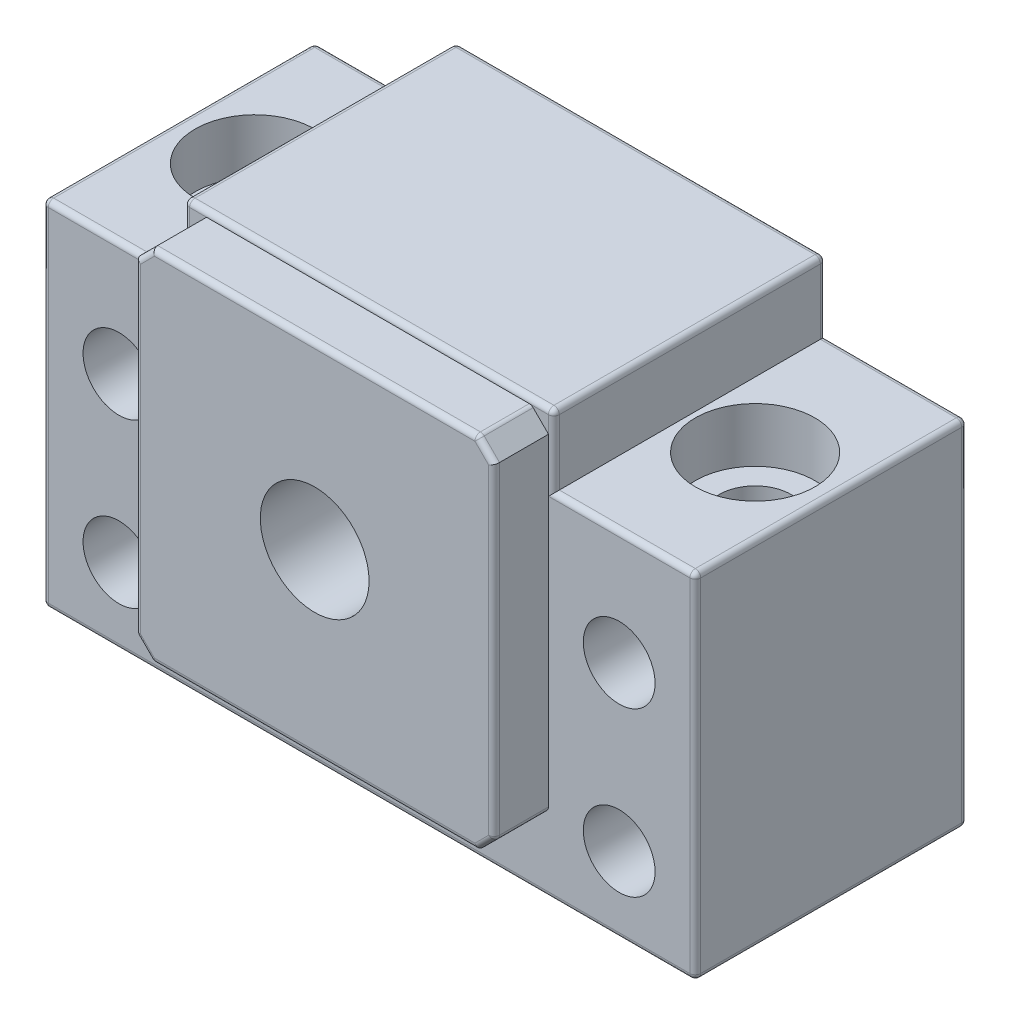
SolidWorks part; units mm, degrees
ref_plane "前视基准面" through (0, 0, 0) normal (0, 0, 1) x (1, 0, 0)
ref_plane "上视基准面" through (0, 0, 0) normal (0, 1, 0) x (1, 0, 0)
ref_plane "右视基准面" through (0, 0, 0) normal (1, 0, 0) x (0, 0, -1)
other "Configuration Table"
sketch "草图1" plane through (0, 0, 0) normal (0, 0, 1) x (1, 0, 0)
  line L0 (0, 22.75) -> (0, 16.25)
  line L1 (-30, 16.25) -> (30, 16.25)
  line L2 (-30, 16.25) -> (-30, -16.25)
  line L3 (-30, -16.25) -> (30, -16.25)
  line L4 (30, 16.25) -> (30, -16.25)
  line L5 (-30, 16.25) -> (30, -16.25) construction
  line L6 (-30, -16.25) -> (30, 16.25) construction
  line L7 (-17, 22.75) -> (17, 22.75)
  line L8 (-17, 22.75) -> (-17, 16.25)
  line L9 (-17, 16.25) -> (17, 16.25)
  line L10 (17, 22.75) -> (17, 16.25)
  line L11 (-17, 22.75) -> (17, 16.25) construction
  line L12 (-17, 16.25) -> (17, 22.75) construction
  line L13 (0, 0) -> (0, 16.25)
  line L14 (-16, 19.0887) -> (-13.3387, 21.75)
  line L15 (-16, 21.75) -> (16, 21.75)
  line L16 (-16, 21.75) -> (-16, -10.25)
  line L17 (-16, -10.25) -> (16, -10.25)
  line L18 (16, 21.75) -> (16, -10.25)
  line L19 (-16, 21.75) -> (16, -10.25) construction
  line L20 (-16, -10.25) -> (16, 21.75) construction
  line L21 (16, 19.0887) -> (13.3387, 21.75)
  line L22 (0, 5.75) -> (16, 5.75)
  line L23 (16, -7.5887) -> (13.3387, -10.25)
  line L24 (-16, -7.5887) -> (-13.3387, -10.25)
  circle A0 centre (-23, -9.25) radius 3.3
  circle A1 centre (-23, 5.75) radius 3.3
  circle A2 centre (23, -9.25) radius 3.3
  circle A3 centre (23, 5.75) radius 3.3
  circle A4 centre (0, 5.75) radius 5
  point P0 (0, 0)
  point P6 (0, 19.5)
  point P22 (0, 5.75)
  dimension "D5" = 6.6
  dimension "D6" = 6.6
  dimension "D14" = 10
  dimension "D1" = 60
  dimension "D2" = 32.5
  dimension "D3" = 6.5
  dimension "D4" = 34
  dimension "D7" = 7
  dimension "D8" = 7
  dimension "D9" = 15
  dimension "D10" = 7
  dimension "D11" = 32
  dimension "D12" = 32
  dimension "D13" = 22
extrude "凸台-拉伸1" add sketch "草图1" along normal blind 25
sketch "草图3" plane through (0, 0, 25) normal (0, 0, 1) x (1, 0, 0)
  line L0 (-16.5, 20.693) -> (-14.943, 22.25)
  line L1 (-16.5, 22.25) -> (16.5, 22.25)
  line L2 (-16.5, 22.25) -> (-16.5, -10.75)
  line L3 (-16.5, -10.75) -> (16.5, -10.75)
  line L4 (16.5, 22.25) -> (16.5, -10.75)
  line L5 (-16.5, 22.25) -> (16.5, -10.75) construction
  line L6 (-16.5, -10.75) -> (16.5, 22.25) construction
  line L7 (0, 5.75) -> (0, 22.25)
  line L8 (0, 5.75) -> (-16.5, 5.75)
  line L9 (16.5, 20.693) -> (14.943, 22.25)
  line L10 (16.5, -9.193) -> (14.943, -10.75)
  line L11 (-16.5, -9.193) -> (-14.943, -10.75)
  point P0 (0, 5.75)
  circle M17 centre (0, 5.75) radius 5
  dimension "D1" = 33
  dimension "D2" = 33
extrude "凸台-拉伸3" add sketch "草图3" along normal blind 5 contours L8 L7 L1 L0 L2 M17 | L2 L11 L3 L10 L4 L9 L1 L7 L8 M17
sketch "草图4" plane through (0, 16.25, 0) normal (0, 1, 0) x (1, 0, 0)
  line L0 (-30, -25) -> (-30, 0) construction
  line L1 (0, 0) -> (0, -25)
  line L2 (-17, -25) -> (17, -25) construction
  line L3 (-30, 0) -> (-17, 0) construction
  circle A0 centre (-23, -12.5) radius 5.5
  circle A1 centre (23, -12.5) radius 5.5
  dimension "D1" = 11
  dimension "D2" = 7
  dimension "D3" = 12.5
extrude "切除-拉伸1" cut sketch "草图4" against normal blind 5 and the other way through all contours A0 | A1
fillet "圆角2" radius 0.5 8 edges at (15.7215, -9.9715, 30) (16.5, 5.75, 30) (0, 22.25, 30) (-15.7215, 21.4715, 30) (-16.5, 5.75, 30) (-15.7215, -9.9715, 30) (0, -10.75, 30) (15.7215, 21.4715, 30)
fillet "圆角3" radius 0.5 8 edges at (23.5, 16.25, 25) (17, 19.5, 25) (0, 22.75, 25) (-17, 19.5, 25) (-23.5, 16.25, 25) (-30, 0, 25) (0, -16.25, 25) (30, 0, 25)
fillet "圆角4" radius 0.5 2 edges at (14.943, 22.25, 27.25) (14.8823, 22.1036, 29.8536)
fillet "圆角5" radius 0.5 2 edges at (16.5, -9.193, 27.25) (16.3536, -9.1323, 29.8536)
fillet "圆角6" radius 0.5 2 edges at (-14.8823, -10.6036, 29.8536) (-14.943, -10.75, 27.25)
fillet "圆角7" radius 0.5 2 edges at (-16.3536, -9.1323, 29.8536) (-16.5, -9.193, 27.25)
fillet "圆角8" radius 0.5 5 edges at (17, 22.75, 12.25) (-17, 22.75, 12.25) (16.8536, 22.6036, 24.8536) (-16.8536, 22.6036, 24.8536) (0, 22.75, 0)
fillet "圆角9" radius 0.5 2 edges at (-30, -16.25, 12.25) (-29.8536, -16.1036, 24.8536)
fillet "圆角10" radius 0.5 2 edges at (30, -16.25, 12.25) (29.8536, -16.1036, 24.8536)
fillet "圆角11" radius 0.5 7 edges at (-30, 16.25, 12.25) (-29.8536, 16.1036, 24.8536) (30, 0.25, 0) (-30, 0.25, 0) (0, -16.25, 0) (-29.8536, -16.1036, 0) (29.8536, -16.1036, 0)
fillet "圆角12" radius 0.5 4 edges at (30, 16.25, 12.5) (29.8536, 16.1036, 24.8536) (23.25, 16.25, 0) (29.8536, 16.25, 0.1464)
fillet "圆角13" radius 0.5 2 edges at (-23.25, 16.25, 0) (-29.8536, 16.1036, 0.1464)
fillet "圆角14" radius 0.5 3 edges at (-17, 19, 0) (-16.8536, 22.6036, 0.1464) (-17, 16.1036, 0.1464)
fillet "圆角15" radius 0.5 3 edges at (17, 19, 0) (16.8536, 22.6036, 0.1464) (17, 16.1036, 0.1464)
sketch "草图5" plane through (0, 11.25, 0) normal (0, 1, 0) x (1, 0, 0)
  circle A0 centre (-23, -12.5) radius 3.3
  circle A1 centre (23, -12.5) radius 3.3
  dimension "D1" = 6.6
  dimension "D2" = 6.6
extrude "切除-拉伸2" cut sketch "草图5" against normal blind 48
